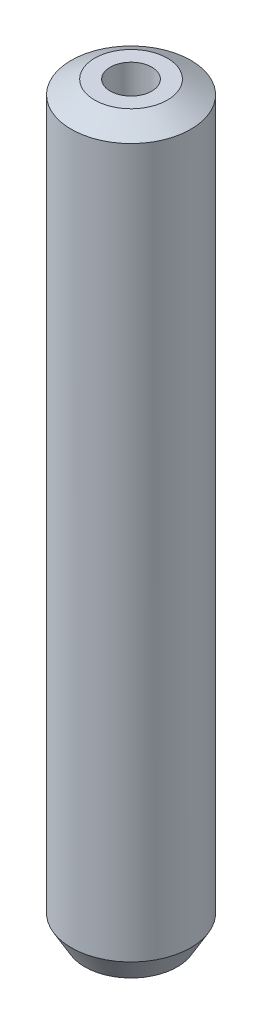
SolidWorks part; units mm, degrees
ref_plane "Front Plane" through (0, 0, 0) normal (0, 0, 1) x (1, 0, 0)
ref_plane "Top Plane" through (0, 0, 0) normal (0, 1, 0) x (1, 0, 0)
ref_plane "Right Plane" through (0, 0, 0) normal (1, 0, 0) x (0, 0, -1)
sketch "Sketch1" plane through (0, 0, 0) normal (0, 1, 0) x (1, 0, 0)
  circle A0 centre (0, 0) radius 7.5
  dimension "SHAFT_OD" = 15
extrude "Boss-Extrude1" add sketch "Sketch1" along normal blind 93.5535
sketch "Sketch2" plane through (0, 0, 0) normal (0, 1, 0) x (1, 0, 0)
  circle A0 centre (0, 0) radius 2.6065
  dimension "BORE_D" = 5.2131
extrude "Cut-Extrude1" cut sketch "Sketch2" along normal through all
chamfer "Chamfer1" distance 1.6981 angle 60 2 edges at (0, 93.5535, 7.5) (0, 0, 7.5) first distance on face at (0, 93.5535, 7.5) first distance on face at (0, 0, 2.6065)
